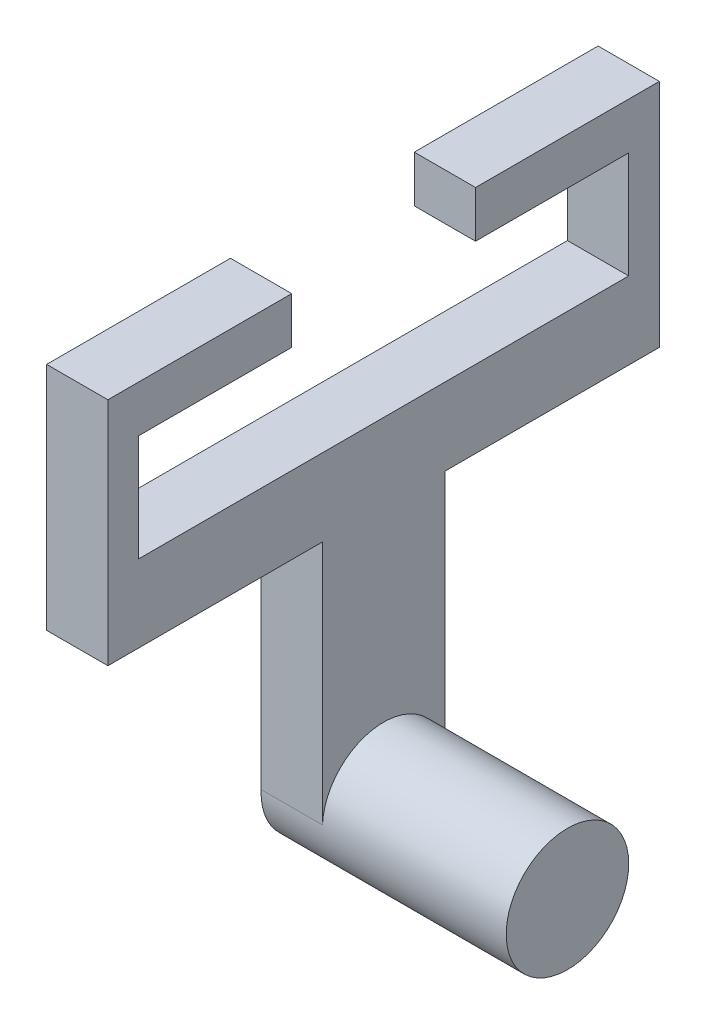
SolidWorks part; units mm, degrees
material "6061-T6 (SS)"
ref_plane "Front Plane" through (0, 0, 0) normal (0, 0, 1) x (1, 0, 0)
ref_plane "Top Plane" through (0, 0, 0) normal (0, 1, 0) x (1, 0, 0)
ref_plane "Right Plane" through (0, 0, 0) normal (1, 0, 0) x (0, 0, -1)
sketch "Sketch2" plane through (0, 0, 0) normal (1, 0, 0) x (0, 0, -1)
  circle A0 centre (0, 0) radius 12.7
  dimension "D1" = 25.4
extrude "Boss-Extrude1" add sketch "Sketch2" along normal blind 50.8 contours A0
sketch "Sketch3" plane through (0, 0, 0) normal (-1, 0, 0) x (0, 0, 1)
  line L1 (-12.6854, 0.6087) -> (12.7146, 0.6087)
  line L2 (-12.6854, 0.6087) -> (-12.6854, 51.4087)
  line L3 (-12.6854, 51.4087) -> (12.7146, 51.4087)
  line L4 (12.7146, 0.6087) -> (12.7146, 51.4087)
  circle A0 centre (0, 0) radius 12.7 construction
  dimension "D1" = 25.4
  dimension "D2" = 50.8
extrude "Boss-Extrude2" add sketch "Sketch3" against normal blind 12.7
sketch "Sketch5" plane through (0, 0, 0) normal (1, 0, 0) x (0, 0, -1)
  line L1 (50.8, 67.3933) -> (-50.8, 67.3933)
  line L2 (50.8, 67.3933) -> (50.8, 51.3913)
  line L3 (50.8, 51.3913) -> (-50.8, 51.3913)
  line L4 (-50.8, 67.3933) -> (-50.8, 51.3913)
  line L5 (50.8, 67.3933) -> (-50.8, 51.3913) construction
  line L6 (50.8, 51.3913) -> (-50.8, 67.3933) construction
  point P0 (0, 59.3923)
  dimension "D1" = 101.6
  dimension "D2" = 16.002
extrude "Boss-Extrude3" add sketch "Sketch5" along normal blind 12.7 separate body
sketch "Sketch6" plane through (0, 0, 0) normal (1, 0, 0) x (0, 0, -1)
  line L1 (-50.8, 51.3913) -> (-57.15, 51.3913)
  line L2 (-50.8, 51.3913) -> (-50.8, 89.4913)
  line L3 (-50.8, 89.4913) -> (-57.15, 89.4913)
  line L4 (-57.15, 51.3913) -> (-57.15, 89.4913)
  line L5 (50.8, 51.3913) -> (57.15, 51.3913)
  line L6 (50.8, 51.3913) -> (50.8, 89.4913)
  line L7 (50.8, 89.4913) -> (57.15, 89.4913)
  line L8 (57.15, 51.3913) -> (57.15, 89.4913)
  dimension "D1" = 6.35
  dimension "D2" = 38.1
  dimension "D3" = 6.35
  dimension "D4" = 38.1
extrude "Boss-Extrude4" add sketch "Sketch6" along normal blind 12.7
sketch "Sketch7" plane through (0, 0, 0) normal (1, 0, 0) x (0, 0, -1)
  line L1 (-57.15, 89.4913) -> (-19.05, 89.4913)
  line L2 (-57.15, 89.4913) -> (-57.15, 99.1433)
  line L3 (-57.15, 99.1433) -> (-19.05, 99.1433)
  line L4 (-19.05, 89.4913) -> (-19.05, 99.1433)
  line L5 (57.15, 89.4913) -> (19.05, 89.4913)
  line L6 (57.15, 89.4913) -> (57.15, 99.1433)
  line L7 (57.15, 99.1433) -> (19.05, 99.1433)
  line L8 (19.05, 89.4913) -> (19.05, 99.1433)
  dimension "D1" = 38.1
  dimension "D2" = 38.1
  dimension "D3" = 9.652
  dimension "D4" = 9.652
extrude "Boss-Extrude5" add sketch "Sketch7" along normal blind 12.7
combine bodies "Combine1" operation type add bodies to combine 102 105
equation "\"d_A\"= 1.00in"
equation "\"t_B\"= 0.50in"
equation "\"h_B\"= 2.00in"
equation "\"h_C\"= 0.625in"
equation "\"L_C\"= 4.00in"
equation "\"L_D\"= 1.500in"
equation "\"h_E\"= 0.375in"
equation "\"L_E\"= 1.500in"
equation "\"W_B\"= \"d_A\""
equation "\"L_A\"= 2.00in"
equation "\"t_C\"= \"t_B\""
equation "\"t_D\"= \"t_B\""
equation "\"t_E\"= \"t_B\""
